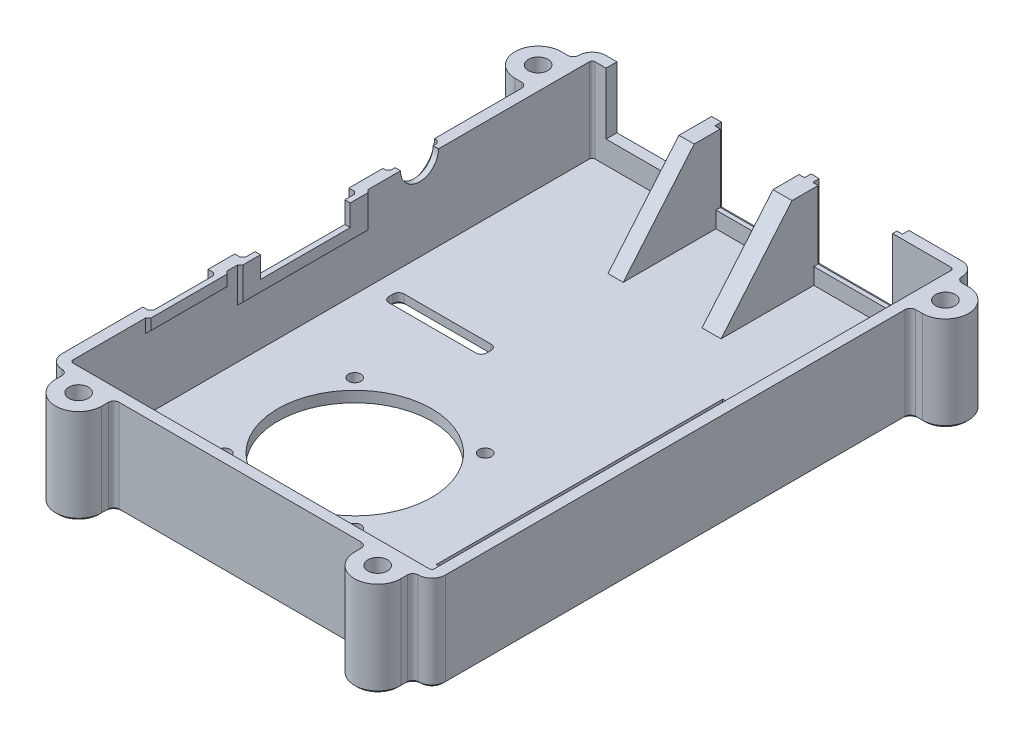
SolidWorks part; units mm, degrees
ref_plane "Front Plane" through (0, 0, 0) normal (0, 0, 1) x (1, 0, 0)
ref_plane "Top Plane" through (0, 0, 0) normal (0, 1, 0) x (1, 0, 0)
ref_plane "Right Plane" through (0, 0, 0) normal (1, 0, 0) x (0, 0, -1)
sketch "Sketch2" plane through (0, 0, 0) normal (0, 1, 0) x (1, 0, 0)
  line L1 (2.5, 0) -> (68, 0)
  line L2 (0, 2.5) -> (0, 97.5)
  line L3 (2.5, 100) -> (68, 100)
  line L4 (70.5, 2.5) -> (70.5, 97.5)
  arc A0 (0, 2.5) -> (2.5, 0) centre (2.5, 2.5) ccw
  arc A1 (68, 0) -> (70.5, 2.5) centre (68, 2.5) ccw
  arc A2 (70.5, 97.5) -> (68, 100) centre (68, 97.5) ccw
  arc A3 (2.5, 100) -> (0, 97.5) centre (2.5, 97.5) ccw
  point P7 (0, 0)
  point P10 (70.5, 0)
  point P13 (70.5, 100)
  point P16 (0, 100)
  dimension "D3" = 2.5
  dimension "D1" = 70.5
  dimension "D2" = 100
extrude "Base" add sketch "Sketch2" along normal blind 17.5
shell "Shell" thickness 2 removed face at (35.25, 17.5, -50)
sketch "Sketch14" plane through (0, 0, 0) normal (0, -1, 0) x (1, 0, 0)
  line L0 (35.25, 0) -> (35.25, -100) construction
  line L2 (68, -100) -> (2.5, -100) construction
  line L3 (-2.2, -88) -> (0, -88)
  line L4 (0, -97.5) -> (0, -2.5) construction
  line L5 (0, -88) -> (0, -96.5)
  line L6 (0, -96.5) -> (-2.2, -96.5)
  line L7 (3.5, 2.2) -> (3.5, 0)
  line L8 (2.5, 0) -> (68, 0) construction
  line L9 (3.5, 0) -> (12, 0)
  line L10 (12, 0) -> (12, 2.2)
  line L11 (72.7, -88) -> (70.5, -88)
  line L12 (70.5, -96.5) -> (72.7, -96.5)
  line L13 (70.5, -88) -> (70.5, -96.5)
  line L14 (58.5, 0) -> (58.5, 2.2)
  line L15 (67, 0) -> (58.5, 0)
  line L16 (67, 2.2) -> (67, 0)
  line L17 (2.5, 0) -> (68, 0) construction
  arc A0 (-2.2, -88) -> (-2.2, -96.5) centre (-2.2, -92.25) ccw
  arc A1 (3.5, 2.2) -> (12, 2.2) centre (7.75, 2.2) cw
  arc A2 (72.7, -88) -> (72.7, -96.5) centre (72.7, -92.25) cw
  arc A3 (67, 2.2) -> (58.5, 2.2) centre (62.75, 2.2) ccw
  dimension "D1" = 2.2
  dimension "D2" = 8.5
  dimension "D3" = 3.5
  dimension "D4" = 3.5
extrude "Clamps" add sketch "Sketch14" against normal up to surface (17.5 mm away) up to face at (35.25, 17.5, -50)
fillet "Clamp Fillets" radius 1 8 edges at (58.5, 8.75, 0) (67, 8.75, 0) (12, 8.75, 0) (3.5, 8.75, 0) (0, 8.75, -96.5) (0, 8.75, -88) (70.5, 8.75, -88) (70.5, 8.75, -96.5)
sketch "Sketch20" plane through (0, 0, 0) normal (0, -1, 0) x (1, 0, 0)
  circle A0 centre (7.75, 2.2) radius 1.8
  circle A1 centre (62.75, 2.2) radius 1.8
  circle A2 centre (72.7, -92.25) radius 1.8
  circle A3 centre (-2.2, -92.25) radius 1.8
  arc A4 (12, 2.2) -> (3.5, 2.2) centre (7.75, 2.2) ccw construction
  arc A5 (67, 2.2) -> (58.5, 2.2) centre (62.75, 2.2) ccw construction
  arc A6 (-2.2, -88) -> (-2.2, -96.5) centre (-2.2, -92.25) ccw construction
  arc A7 (72.7, -96.5) -> (72.7, -88) centre (72.7, -92.25) ccw construction
  dimension "D1" = 3.6
extrude "Clamp Holes" cut sketch "Sketch20" against normal through all
sketch "Sketch21" plane through (0, 0, 0) normal (0, -1, 0) x (1, 0, 0)
  circle A0 centre (7.75, 2.2) radius 2.9
  circle A1 centre (62.75, 2.2) radius 2.9
  circle A2 centre (72.7, -92.25) radius 2.9
  circle A3 centre (-2.2, -92.25) radius 2.9
  circle A4 centre (-2.2, -92.25) radius 1.8 construction
  circle A5 centre (7.75, 2.2) radius 1.8 construction
  circle A6 centre (62.75, 2.2) radius 1.8 construction
  circle A7 centre (72.7, -92.25) radius 1.8 construction
  dimension "D1" = 5.8
extrude "Clamp Countersinks" cut sketch "Sketch21" against normal blind 3.4
chamfer "Clamp Countersink Chamfers" distance 0.3 angle 45 4 edges at (-2.2, 0, -95.15) (72.7, 0, -95.15) (62.75, 0, -0.7) (7.75, 0, -0.7)
sketch "Sketch24" plane through (0, 0, -100) normal (0, 0, -1) x (-1, 0, 0)
  line L0 (-68, 17.5) -> (-2.5, 17.5) construction
  line L1 (-57.25, 17.5) -> (-42.75, 17.5)
  line L2 (-57.25, 17.5) -> (-57.25, 5)
  line L3 (-57.25, 5) -> (-42.75, 5)
  line L4 (-42.75, 17.5) -> (-42.75, 5)
  line L6 (0, 17.5) -> (0, 0) construction
  line L7 (-39.25, 17.5) -> (-24.75, 17.5)
  line L8 (-39.25, 17.5) -> (-39.25, 5)
  line L9 (-39.25, 5) -> (-24.75, 5)
  line L10 (-24.75, 17.5) -> (-24.75, 5)
  dimension "D1" = 14.5
  dimension "D2" = 24.75
  dimension "D3" = 42.75
  dimension "D4" = 12.5
extrude "USB Cutout" cut sketch "Sketch24" against normal blind 18.25
sketch "Sketch25" plane through (0, 0, -100) normal (0, 0, -1) x (-1, 0, 0)
  line L0 (-42.75, 17.5) -> (-39.25, 17.5) construction
  line L1 (-41.75, 17.5) -> (-58.25, 17.5)
  line L2 (-41.75, 17.5) -> (-41.75, 4)
  line L3 (-41.75, 4) -> (-58.25, 4)
  line L4 (-58.25, 17.5) -> (-58.25, 4)
  line L6 (-24.75, 17.5) -> (-2.5, 17.5) construction
  line L7 (-23.75, 17.5) -> (-40.25, 17.5)
  line L8 (-23.75, 17.5) -> (-23.75, 4)
  line L9 (-23.75, 4) -> (-40.25, 4)
  line L10 (-40.25, 17.5) -> (-40.25, 4)
  line L12 (-57.25, 17.5) -> (-57.25, 5) construction
  line L13 (-42.75, 5) -> (-42.75, 17.5) construction
  line L14 (-39.25, 17.5) -> (-39.25, 5) construction
  line L15 (-24.75, 5) -> (-24.75, 17.5) construction
  point P18 (-57.25, 11.25)
  dimension "D1" = 1
  dimension "D2" = 1
  dimension "D3" = 1
  dimension "D4" = 1
  dimension "D5" = 13.5
extrude "USB Approach" cut sketch "Sketch25" against normal blind 1.2
sketch "Sketch26" plane through (42.75, 0, 0) normal (1, 0, 0) x (0, 0, -1)
  line L0 (98, 2) -> (98, 17.5)
  line L1 (98, 17.5) -> (94, 17.5)
  line L2 (98, 2) -> (80.95, 2)
  line L3 (80.95, 2) -> (94, 17.5)
  line L4 (100, 4) -> (100, 17.5) construction
  line L5 (100, 4) -> (100, 17.5) construction
  dimension "D1" = 6
  dimension "D2" = 19.05
extrude "USB Inner Support" add sketch "Sketch26" against normal up to surface (3.5 mm away) up to face at (39.25, 11.25, -98.4)
sketch "Sketch27" plane through (24.75, 0, 0) normal (1, 0, 0) x (0, 0, -1)
  line L0 (98, 2) -> (98, 17.5)
  line L1 (98, 17.5) -> (94, 17.5)
  line L2 (98, 2) -> (80.95, 2)
  line L3 (80.95, 2) -> (94, 17.5)
  line L4 (100, 4) -> (100, 17.5) construction
  line L5 (100, 4) -> (100, 17.5) construction
  dimension "D1" = 6
  dimension "D2" = 19.05
extrude "USB Outer Support" add sketch "Sketch27" against normal blind 2.8
sketch "Sketch28" plane through (0, 0, -100) normal (0, 0, -1) x (-1, 0, 0)
  line L0 (-23.75, 17.5) -> (-2.5, 17.5) construction
  line L1 (-21.95, 17.5) -> (-4.55, 17.5)
  line L2 (-21.95, 17.5) -> (-21.95, 6.2)
  line L3 (-21.95, 6.2) -> (-4.55, 6.2)
  line L4 (-4.55, 17.5) -> (-4.55, 6.2)
  line L5 (0, 17.5) -> (0, 0) construction
  dimension "D1" = 17.4
  dimension "D2" = 4.55
  dimension "D3" = 11.3
extrude "RJ45 Cutout" cut sketch "Sketch28" against normal blind 22.7
sketch "Sketch29" plane through (2, 0, 0) normal (1, 0, 0) x (0, 0, -1)
  line L0 (97.5, 17.5) -> (2.5, 17.5) construction
  line L1 (15.85, 17.5) -> (30.85, 17.5)
  line L2 (15.85, 17.5) -> (15.85, 15)
  line L3 (15.85, 15) -> (30.85, 15)
  line L4 (30.85, 17.5) -> (30.85, 15)
  line L5 (0, 17.5) -> (0, 0) construction
  line L6 (32.75, 17.5) -> (56.75, 17.5)
  line L7 (32.75, 17.5) -> (32.75, 11.07)
  line L8 (32.75, 11.07) -> (56.75, 11.07)
  line L9 (56.75, 17.5) -> (56.75, 11.07)
  dimension "D1" = 24
  dimension "D2" = 15
  dimension "D3" = 15.85
  dimension "D4" = 32.75
  dimension "D5" = 2.5
  dimension "D6" = 6.43
extrude "HDMI Support" add sketch "Sketch29" along normal blind 0.5
chamfer "HDMI Support Chamfer" distance 0.5 angle 45 6 edges at (2.5, 14.285, -56.75) (2.5, 11.07, -44.75) (2.5, 14.285, -32.75) (2.5, 16.25, -30.85) (2.5, 15, -23.35) (2.5, 16.25, -15.85)
sketch "Sketch30" plane through (0, 0, 0) normal (-1, 0, 0) x (0, 0, 1)
  line L0 (-87, 17.5) -> (-2.5, 17.5) construction
  line L1 (-34.25, 17.5) -> (-55.25, 17.5)
  line L2 (-34.25, 17.5) -> (-34.25, 11.57)
  line L3 (-34.25, 11.57) -> (-55.25, 11.57)
  line L4 (-55.25, 17.5) -> (-55.25, 11.57)
  line L5 (0, 17.5) -> (0, 0) construction
  line L6 (-29.35, 17.5) -> (-17.35, 17.5)
  line L7 (-29.35, 17.5) -> (-29.35, 15.5)
  line L8 (-29.35, 15.5) -> (-17.35, 15.5)
  line L9 (-17.35, 17.5) -> (-17.35, 15.5)
  dimension "D1" = 12
  dimension "D2" = 21
  dimension "D3" = 17.35
  dimension "D4" = 34.25
  dimension "D5" = 5.93
  dimension "D6" = 2
extrude "HDMI Approach" cut sketch "Sketch30" against normal blind 1.5
sketch "Sketch31" plane through (1.5, 0, 0) normal (-1, 0, 0) x (0, 0, 1)
  line L0 (-34.25, 17.5) -> (-55.25, 17.5) construction
  line L1 (-53, 17.5) -> (-36.5, 17.5)
  line L2 (-53, 17.5) -> (-53, 13.57)
  line L3 (-53, 13.57) -> (-36.5, 13.57)
  line L4 (-36.5, 17.5) -> (-36.5, 13.57)
  line L5 (-55.25, 17.5) -> (-55.25, 11.57) construction
  line L6 (-34.25, 11.57) -> (-34.25, 17.5) construction
  line L7 (-55.25, 11.57) -> (-34.25, 11.57) construction
  dimension "D1" = 2.25
  dimension "D2" = 2.25
  dimension "D3" = 2
extrude "HDMI Cutout" cut sketch "Sketch31" against normal blind 1
chamfer "HDMI Approach Chamfer" distance 0.5 angle 45 6 edges at (1.5, 16.5, -17.35) (1.5, 15.5, -23.35) (1.5, 16.5, -29.35) (1.5, 14.535, -34.25) (1.5, 11.57, -44.75) (1.5, 14.535, -55.25)
sketch "Sketch32" plane through (0, 0, 0) normal (-1, 0, 0) x (0, 0, 1)
  line L0 (-87, 17.5) -> (-55.25, 17.5) construction
  line L1 (0, 17.5) -> (0, 0) construction
  circle A0 centre (-66.25, 17.5) radius 3.5
  dimension "D1" = 7
  dimension "D2" = 66.25
extrude "Audio Cutout" cut sketch "Sketch32" against normal blind 2
sketch "Sketch33" plane through (0, 0, 0) normal (-1, 0, 0) x (0, 0, 1)
  circle A0 centre (-66.25, 17.5) radius 4.75
  arc A1 (-69.75, 17.5) -> (-62.75, 17.5) centre (-66.25, 17.5) ccw construction
  dimension "D1" = 9.5
extrude "Audio Approach" cut sketch "Sketch33" against normal blind 1
chamfer "Audio Approach Chamfer" distance 0.5 angle 45 1 edges at (1, 12.75, -66.25)
sketch "Sketch34" plane through (0, 0, 0) normal (0, -1, 0) x (1, 0, 0)
  line L0 (70.5, -2.5) -> (70.5, -87) construction
  line L1 (52.5, -18.8) -> (58.5, -18.8)
  line L2 (52.5, -18.8) -> (52.5, -71.5)
  line L3 (52.5, -71.5) -> (58.5, -71.5)
  line L4 (58.5, -18.8) -> (58.5, -71.5)
  line L5 (13, 0) -> (57.5, 0) construction
  point P6 (55.5, -18.8)
  dimension "D1" = 6
  dimension "D2" = 52.7
  dimension "D3" = 12
  dimension "D4" = 18.8
extrude "Header Cutout" cut sketch "Sketch34" against normal blind 2
sketch "Sketch35" plane through (0, 0, 0) normal (0, -1, 0) x (1, 0, 0)
  line L0 (55.5, -18.8) -> (55.5, -71.5) construction
  line L1 (58.5, -18.8) -> (52.5, -18.8) construction
  line L2 (52.5, -71.5) -> (58.5, -71.5) construction
  line L3 (52.5, -45.15) -> (58.5, -45.15) construction
  line L4 (52.5, -18.8) -> (52.5, -71.5) construction
  line L5 (58.5, -71.5) -> (58.5, -18.8) construction
  line L6 (56, -18.8) -> (55, -18.8)
  line L7 (55, -18.8) -> (55, -19.8)
  line L8 (55, -19.8) -> (53.5, -19.8)
  line L9 (53.5, -19.8) -> (53.5, -24.7625)
  line L10 (53.5, -24.7625) -> (52.5, -24.7625)
  line L11 (52.5, -24.7625) -> (52.5, -25.7625)
  line L12 (52.5, -25.7625) -> (53.5, -25.7625)
  line L13 (53.5, -25.7625) -> (53.5, -37.6875)
  line L14 (53.5, -37.6875) -> (52.5, -37.6875)
  line L15 (52.5, -37.6875) -> (52.5, -38.6875)
  line L16 (52.5, -38.6875) -> (53.5, -38.6875)
  line L17 (53.5, -38.6875) -> (53.5, -43.65)
  line L18 (53.5, -43.65) -> (55, -43.65)
  line L19 (55, -43.65) -> (55, -44.65)
  line L20 (55, -44.65) -> (52.5, -44.65)
  line L21 (52.5, -44.65) -> (52.5, -45.65)
  line L22 (56, -71.5) -> (55, -71.5)
  line L23 (55, -45.65) -> (52.5, -45.65)
  line L24 (55, -46.65) -> (55, -45.65)
  line L25 (53.5, -46.65) -> (55, -46.65)
  line L26 (53.5, -51.6125) -> (53.5, -46.65)
  line L27 (52.5, -51.6125) -> (53.5, -51.6125)
  line L28 (52.5, -52.6125) -> (52.5, -51.6125)
  line L29 (53.5, -52.6125) -> (52.5, -52.6125)
  line L30 (53.5, -64.5375) -> (53.5, -52.6125)
  line L31 (52.5, -64.5375) -> (53.5, -64.5375)
  line L32 (52.5, -65.5375) -> (52.5, -64.5375)
  line L33 (53.5, -65.5375) -> (52.5, -65.5375)
  line L34 (53.5, -70.5) -> (53.5, -65.5375)
  line L35 (55, -70.5) -> (53.5, -70.5)
  line L36 (55, -71.5) -> (55, -70.5)
  line L37 (56, -71.5) -> (56, -70.5)
  line L38 (56, -70.5) -> (57.5, -70.5)
  line L39 (57.5, -70.5) -> (57.5, -65.5375)
  line L40 (57.5, -65.5375) -> (58.5, -65.5375)
  line L41 (58.5, -65.5375) -> (58.5, -64.5375)
  line L42 (58.5, -64.5375) -> (57.5, -64.5375)
  line L43 (57.5, -64.5375) -> (57.5, -52.6125)
  line L44 (57.5, -52.6125) -> (58.5, -52.6125)
  line L45 (58.5, -52.6125) -> (58.5, -51.6125)
  line L46 (58.5, -51.6125) -> (57.5, -51.6125)
  line L47 (57.5, -51.6125) -> (57.5, -46.65)
  line L48 (57.5, -46.65) -> (56, -46.65)
  line L49 (56, -46.65) -> (56, -45.65)
  line L50 (56, -45.65) -> (58.5, -45.65)
  line L51 (58.5, -44.65) -> (58.5, -45.65)
  line L52 (56, -44.65) -> (58.5, -44.65)
  line L53 (56, -43.65) -> (56, -44.65)
  line L54 (57.5, -43.65) -> (56, -43.65)
  line L55 (57.5, -38.6875) -> (57.5, -43.65)
  line L56 (58.5, -38.6875) -> (57.5, -38.6875)
  line L57 (58.5, -37.6875) -> (58.5, -38.6875)
  line L58 (57.5, -37.6875) -> (58.5, -37.6875)
  line L59 (57.5, -25.7625) -> (57.5, -37.6875)
  line L60 (58.5, -25.7625) -> (57.5, -25.7625)
  line L61 (58.5, -24.7625) -> (58.5, -25.7625)
  line L62 (57.5, -24.7625) -> (58.5, -24.7625)
  line L63 (57.5, -19.8) -> (57.5, -24.7625)
  line L64 (56, -19.8) -> (57.5, -19.8)
  line L65 (56, -18.8) -> (56, -19.8)
  dimension "D1" = 0.5
  dimension "D2" = 1
  dimension "D3" = 1.5
  dimension "D4" = 11.925
extrude "Header Cover" add sketch "Sketch35" against normal blind 1
chamfer "Shell Chamfer" distance 0.5 angle 45 44 edges at (53.75, 0, -71.5) (52.5, 0, -68.5187) (52.5, 0, -58.575) (52.5, 0, -48.6313) (52.5, 0, -41.6688) (52.5, 0, -31.725) (52.5, 0, -21.7813) (53.75, 0, -18.8) (57.25, 0, -18.8) (58.5, 0, -21.7813) (58.5, 0, -31.725) (58.5, 0, -41.6688) (58.5, 0, -48.6313) (58.5, 0, -58.575) (58.5, 0, -68.5187) (57.25, 0, -71.5) (69.7678, 0, -99.2678) (70.7929, 0, -96.7929) (72.1, 0, -96.5) (76.95, 0, -92.25) (72.1, 0, -88) (70.7929, 0, -87.7071) (70.5, 0, -44.75) (35.25, 0, -100) (0.7322, 0, -99.2678) (-0.2929, 0, -96.7929) (-1.6, 0, -96.5) (-6.45, 0, -92.25) (-1.6, 0, -88) (0, 0, -44.75) (69.7678, 0, -0.7322) (67.2929, 0, 0.2929) (67, 0, 1.6) (62.75, 0, 6.45) (58.5, 0, 1.6) (58.2071, 0, 0.2929) (0.7322, 0, -0.7322) (3.5, 0, 1.6) (7.75, 0, 6.45) (12, 0, 1.6) (12.2929, 0, 0.2929) (35.25, 0, 0) (-0.2929, 0, -87.7071) (3.2071, 0, 0.2929)
sketch "Sketch38" plane through (0, 0, 0) normal (0, -1, 0) x (1, 0, 0)
  line L0 (68, -100) -> (2.5, -100) construction
  line L1 (6.45, -56.157) -> (22.45, -56.157)
  line L2 (5.45, -57.157) -> (5.45, -57.957)
  line L3 (6.45, -58.957) -> (22.45, -58.957)
  line L4 (23.45, -57.157) -> (23.45, -57.957)
  line L5 (0, -87) -> (0, -2.5) construction
  arc A0 (22.45, -56.157) -> (23.45, -57.157) centre (22.45, -57.157) cw
  arc A1 (23.45, -57.957) -> (22.45, -58.957) centre (22.45, -57.957) cw
  arc A2 (6.45, -58.957) -> (5.45, -57.957) centre (6.45, -57.957) cw
  arc A3 (5.45, -57.157) -> (6.45, -56.157) centre (6.45, -57.157) cw
  point P12 (23.45, -58.957)
  point P15 (5.45, -58.957)
  point P18 (5.45, -56.157)
  dimension "D5" = 1
  dimension "D1" = 18
  dimension "D2" = 2.8
  dimension "D3" = 41.043
  dimension "D4" = 5.45
extrude "Ribbon Slot" cut sketch "Sketch38" against normal up to surface (2 mm away) up to face at (55.5, 2, -45.15)
chamfer "Ribbon Slot Chamfer" distance 0.5 angle 45 8 edges at (14.45, 0, -56.157) (23.1571, 0, -56.4499) (23.45, 0, -57.557) (23.1571, 0, -58.6641) (14.45, 0, -58.957) (5.7429, 0, -58.6641) (5.45, 0, -57.557) (5.7429, 0, -56.4499)
sketch "Sketch39" plane through (0, 0, 0) normal (0, -1, 0) x (1, 0, 0)
  line L0 (0, -87) -> (0, -2.5) construction
  line L1 (13, 0) -> (57.5, 0) construction
  line L2 (27.25, -29.0785) -> (44.2206, -29.0785) construction
  line L3 (27.25, -12.1079) -> (27.25, -43.2285) construction
  line L4 (27.25, -29.0785) -> (39.25, -17.0785) construction
  circle A0 centre (27.25, -29.0785) radius 16.9706 construction
  circle A1 centre (27.25, -29.0785) radius 14.15
  circle A2 centre (39.25, -17.0785) radius 1.15
  circle A3 centre (39.25, -41.0785) radius 1.15
  circle A4 centre (15.25, -41.0785) radius 1.15
  circle A5 centre (15.25, -17.0785) radius 1.15
  dimension "D3" = 33.9412
  dimension "D4" = 28.3
  dimension "D6" = 2.3
  dimension "D1" = 27.25
  dimension "D2" = 29.0785
  dimension "D5" = 45
extrude "Fan Mount" cut sketch "Sketch39" against normal up to surface (2 mm away) up to face at (14.45, 2, -57.557)
